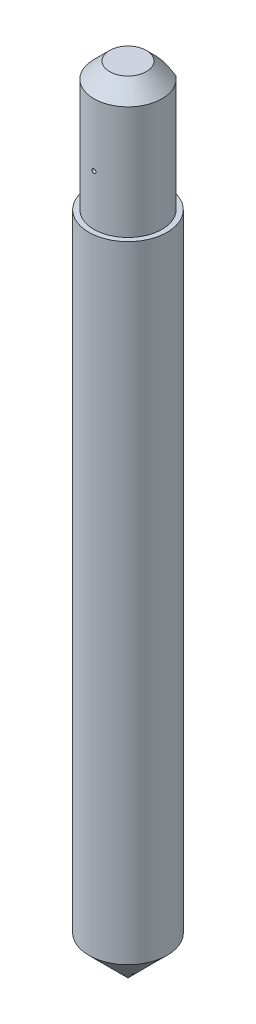
SolidWorks part; units mm, degrees
ref_plane "Front Plane" through (0, 0, 0) normal (0, 0, 1) x (1, 0, 0)
ref_plane "Top Plane" through (0, 0, 0) normal (0, 1, 0) x (1, 0, 0)
ref_plane "Right Plane" through (0, 0, 0) normal (1, 0, 0) x (0, 0, -1)
sketch "Sketch1" plane through (0, 0, 0) normal (0, 1, 0) x (1, 0, 0)
  circle A0 centre (0, 0) radius 5
  dimension "D1" = 10
extrude "Boss-Extrude1" add sketch "Sketch1" along normal blind 85
chamfer "Chamfer1" distance 5 angle 45 1 edges at (0, 0, 5)
sketch "Sketch2" plane through (0, 85, 0) normal (0, 1, 0) x (1, 0, 0)
  line L1 (-2.6495, 3.45) -> (2.6495, 3.45)
  arc A0 (-2.6495, 3.45) -> (2.6495, 3.45) centre (0, 0) ccw
  point P5 (0, -4.35)
  dimension "D1" = 8.7
  dimension "D2" = 7.8
extrude "Boss-Extrude2" add sketch "Sketch2" along normal blind 16.45
chamfer "Chamfer2" distance 2 angle 45 1 edges at (0, 101.45, 4.35)
sketch "Sketch3" plane through (0, 0, 0) normal (1, 0, 0) x (0, 0, -1)
  line L0 (-4.35, 91.2) -> (-4.35, 91.7)
  line L1 (2.35, 101.45) -> (-2.35, 101.45) construction
  line L2 (-4.35, 85) -> (-4.35, 99.45) construction
  line L3 (0, 101.45) -> (0, 0) construction
  arc A0 (-4.35, 91.7) -> (-4.35, 91.2) centre (-4.35, 91.45) cw
  dimension "D1" = 10
  dimension "D2" = 0.5
revolve "Cut-Revolve1" cut sketch "Sketch3" angle 360 about L0
pattern_circular "CirPattern1" [suppressed] count 3 over 360 about axis through (0, 101.45, 0) along (0, -1, 0) of bodies 103
